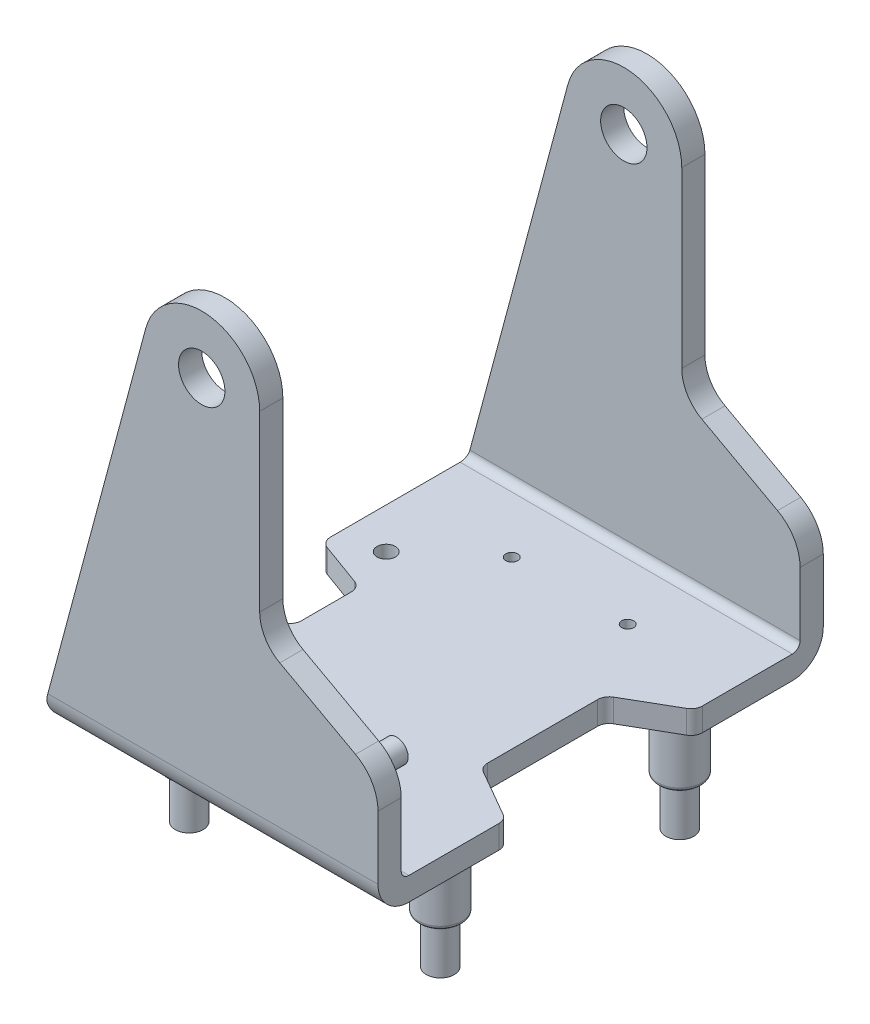
SolidWorks part; units mm, degrees
ref_plane "Front Plane" through (0, 0, 0) normal (0, 0, 1) x (1, 0, 0)
ref_plane "Top Plane" through (0, 0, 0) normal (0, 1, 0) x (1, 0, 0)
ref_plane "Right Plane" through (0, 0, 0) normal (1, 0, 0) x (0, 0, -1)
sketch "Sketch1" plane through (0, 0, 0) normal (0, 1, 0) x (1, 0, 0)
  line L0 (-32.5, 31) -> (-32.5, -31) construction
  line L1 (32.5, 31) -> (32.5, -31) construction
  line L2 (-32.5, 0) -> (32.5, 0) construction
  circle A0 centre (-32.5, 31) radius 3.625
  circle A1 centre (-32.5, -31) radius 3.625
  circle A2 centre (32.5, -31) radius 3.625
  circle A3 centre (32.5, 31) radius 3.625
  point P4 (32.5, 0)
  point P5 (-32.5, 0)
  point P13 (0, 0)
  dimension "D4" = 7.25
  dimension "D1" = 62
  dimension "D2" = 62
  dimension "D3" = 65
extrude "Boss-Extrude1" add sketch "Sketch1" against normal blind 29
sketch "Sketch2" plane through (0, 0, 0) normal (0, 1, 0) x (1, 0, 0)
  line L0 (-43, 34.625) -> (-32.5, 34.625) construction
  line L1 (-43, 57.625) -> (43, 57.625)
  line L2 (-43, 57.625) -> (-43, -57.625)
  line L3 (-43, -57.625) -> (43, -57.625)
  line L4 (43, 57.625) -> (43, -57.625)
  line L5 (-43, 57.625) -> (43, -57.625) construction
  line L6 (-43, -57.625) -> (43, 57.625) construction
  line L7 (-36.125, 57.625) -> (-36.125, 31) construction
  circle A0 centre (-32.5, 31) radius 3.625 construction
  point P0 (0, 0)
  dimension "D1" = 23
  dimension "D2" = 86
extrude "Boss-Extrude2" add sketch "Sketch2" along normal blind 6
sketch "Sketch4" plane through (0, 0, 57.625) normal (0, 0, 1) x (1, 0, 0)
  line L2 (43, 6) -> (-43, 6)
  line L3 (-43, 6) -> (-17.1181, 102.5926)
  line L4 (12.3708, 98.7103) -> (12.3708, 53.7103)
  line L6 (22.3708, 43.7103) -> (43, 43.7103)
  line L7 (43, 43.7103) -> (43, 6)
  arc A1 (-17.1181, 102.5926) -> (12.3708, 98.7103) centre (-2.6292, 98.7103) cw
  arc A2 (12.3708, 53.7103) -> (22.3708, 43.7103) centre (22.3708, 53.7103) ccw
  dimension "D3" = 15
  dimension "D5" = 10
  dimension "D1" = 75
  dimension "D2" = 100
  dimension "D4" = 45
  dimension "D7" = 15
extrude "Boss-Extrude3" add sketch "Sketch4" against normal blind 6
fillet "Fillet2" radius 10 1 edges at (43, 43.7103, 54.625)
mirror "Mirror1" about plane through (0, 0, 0) normal (0, 0, 1) of "Boss-Extrude3", "Fillet2"
sketch "Sketch5" plane through (0, 0, 0) normal (0, -1, 0) x (1, 0, 0)
  circle A0 centre (-32.5, -31) radius 3.625 construction
  circle A1 centre (32.5, -31) radius 3.625 construction
  circle A2 centre (32.5, 31) radius 3.625 construction
  circle A3 centre (-32.5, 31) radius 3.625 construction
  circle A4 centre (-32.5, -31) radius 3.625
  circle A5 centre (32.5, -31) radius 3.625
  circle A6 centre (32.5, 31) radius 3.625
  circle A7 centre (-32.5, 31) radius 3.625
  circle A8 centre (-32.5, 31) radius 5.625
  circle A9 centre (32.5, 31) radius 5.625
  circle A10 centre (32.5, -31) radius 5.625
  circle A11 centre (-32.5, -31) radius 5.625
  dimension "D1" = 2
extrude "Boss-Extrude4" add sketch "Sketch5" along normal blind 17
fillet "Fillet3" radius 2 4 edges at (32.5, 0, -25.375) (32.5, 0, 36.625) (-32.5, 0, 36.625) (-32.5, 0, -25.375)
fillet "Fillet4" radius 1 8 edges at (32.5, -17, -36.625) (32.5, -17, -34.625) (-32.5, -17, -36.625) (-32.5, -17, -34.625) (-32.5, -17, 25.375) (-32.5, -17, 27.375) (32.5, -17, 25.375) (32.5, -17, 27.375)
fillet "Fillet5" radius 8 2 edges at (0, 0, -57.625) (0, 0, 57.625)
fillet "Fillet6" radius 2 2 edges at (0, 6, -51.625) (0, 6, 51.625)
sketch "Sketch6" plane through (0, 6, 0) normal (0, 1, 0) x (1, 0, 0)
  line L0 (-43, 24.625) -> (-28, 15.9647)
  line L1 (-43, 49.625) -> (-43, -49.625) construction
  line L2 (-28, 15.9647) -> (-28, -15.9647)
  line L3 (-28, -15.9647) -> (-43, -24.625)
  line L4 (-43, -24.625) -> (-43, 24.625)
  dimension "D1" = 25
  dimension "D2" = 25
  dimension "D3" = 15
  dimension "D4" = 120
  dimension "D5" = 120
extrude "Cut-Extrude1" cut sketch "Sketch6" against normal through all both and the other way through all
mirror "Mirror2" about plane through (0, 0, 0) normal (1, 0, 0) of "Cut-Extrude1"
fillet "Fillet7" radius 3 8 edges at (-43, 3, 24.625) (-28, 3, 15.9647) (-43, 3, -24.625) (-28, 3, -15.9647) (43, 3, -24.625) (28, 3, -15.9647) (43, 3, 24.625) (28, 3, 15.9647)
sketch "Sketch7" plane through (0, 0, 57.625) normal (0, 0, 1) x (1, 0, 0)
  circle A0 centre (-2.6292, 98.7103) radius 6
  dimension "D1" = 12
extrude "Cut-Extrude2" cut sketch "Sketch7" against normal through all both
sketch "Sketch8" plane through (0, 0, 51.625) normal (0, 0, -1) x (-1, 0, 0)
  line L0 (-43, 8) -> (42.4641, 8) construction
  circle A2 centre (-31.8179, 24.4204) radius 3
  dimension "D1" = 6
  dimension "D2" = 11.1821
  dimension "D3" = 16.4204
sketch "Sketch9" plane through (0, 0, 51.625) normal (0, 0, -1) x (-1, 0, 0)
  line L0 (-43, 8) -> (42.4641, 8) construction
  circle A2 centre (21.2278, 17.4368) radius 3
  dimension "D1" = 9.4368
  dimension "D3" = 6
  dimension "D2" = 21.2363
extrude "Boss-Extrude6" add sketch "Sketch9" along normal blind 10
extrude "Boss-Extrude7" add sketch "Sketch8" along normal blind 10
fillet "Fillet8" radius 2 2 edges at (28.8179, 24.4204, 51.625) (-24.2278, 17.4368, 51.625)
sketch "Sketch12" plane through (0, 0, 0) normal (0, -1, 0) x (1, 0, 0)
  line L1 (-15, 35) -> (15, 35) construction
  line L2 (-15, 35) -> (-15, -35) construction
  line L3 (-15, -35) -> (15, -35) construction
  line L4 (15, 35) -> (15, -35) construction
  line L5 (-15, 35) -> (15, -35) construction
  line L6 (-15, -35) -> (15, 35) construction
  circle A0 centre (-15, 35) radius 1.55
  circle A1 centre (15, 35) radius 1.55
  circle A2 centre (15, -35) radius 1.55
  circle A3 centre (-15, -35) radius 1.55
  point P0 (0, 0)
  dimension "D3" = 3.1
  dimension "D1" = 30
  dimension "D2" = 70
extrude "Cut-Extrude3" cut sketch "Sketch12" against normal through all both and the other way through all
sketch "Sketch13" plane through (0, 6, 0) normal (0, 1, 0) x (1, 0, 0)
  line L0 (-41.5, -23.759) -> (-29.5, -16.8308) construction
  line L1 (-28, -14.2327) -> (-28, 14.2327) construction
  line L2 (-29.5, 16.8308) -> (-41.5, 23.759) construction
  line L3 (-41.5, -23.759) -> (-29.5, -16.8308)
  line L4 (-28, -14.2327) -> (-28, 14.2327)
  line L5 (-29.5, 16.8308) -> (-41.5, 23.759)
  line L6 (-43, -26.3571) -> (-43, 26.3571)
  arc A0 (-41.5, -23.759) -> (-43, -26.3571) centre (-40, -26.3571) ccw construction
  arc A1 (-29.5, -16.8308) -> (-28, -14.2327) centre (-31, -14.2327) ccw construction
  arc A2 (-28, 14.2327) -> (-29.5, 16.8308) centre (-31, 14.2327) ccw construction
  arc A3 (-43, 26.3571) -> (-41.5, 23.759) centre (-40, 26.3571) ccw construction
  arc A4 (-41.5, -23.759) -> (-43, -26.3571) centre (-40, -26.3571) ccw
  arc A5 (-29.5, -16.8308) -> (-28, -14.2327) centre (-31, -14.2327) ccw
  arc A6 (-28, 14.2327) -> (-29.5, 16.8308) centre (-31, 14.2327) ccw
  arc A7 (-43, 26.3571) -> (-41.5, 23.759) centre (-40, 26.3571) ccw
extrude "Boss-Extrude8" add sketch "Sketch13" against normal up to surface (6 mm away) up to face at (-15, 0, -33.45)
sketch "Sketch14" plane through (0, 6, 0) normal (0, 1, 0) x (1, 0, 0)
  line L0 (-43, 14) -> (-43, -14)
  line L1 (-43, 49.625) -> (-43, -49.625) construction
  line L2 (-43, -14) -> (-28, -8.5404)
  line L3 (-28, -8.5404) -> (-28, 8.5404)
  line L4 (-28, 8.5404) -> (-43, 14)
  point P7 (-43, 0)
  point P8 (-28, 0)
  dimension "D1" = 15
  dimension "D2" = 28
  dimension "D3" = 110
extrude "Cut-Extrude4" cut sketch "Sketch14" against normal blind 10
fillet "Fillet9" radius 3 4 edges at (-43, 3, 14) (-28, 3, 8.5404) (-28, 3, -8.5404) (-43, 3, -14)
sketch "Sketch15" plane through (0, 6, 0) normal (0, 1, 0) x (1, 0, 0)
  line L0 (-32.5, 20) -> (-32.5, -20) construction
  line L1 (-28, -6.4398) -> (-28, 6.4398) construction
  line L2 (-43, 49.625) -> (-43, 16.1006) construction
  circle A0 centre (-32.5, 20) radius 2.375
  circle A1 centre (-32.5, -20) radius 2.375
  point P4 (-28, 0)
  point P5 (-32.5, 0)
  dimension "D3" = 4.75
  dimension "D1" = 40
  dimension "D2" = 10.5
extrude "Cut-Extrude5" cut sketch "Sketch15" against normal blind 10
sketch "Sketch16" plane through (0, 0, 51.625) normal (0, 0, -1) x (-1, 0, 0)
  line L0 (-43, 33.7103) -> (-43, 8) construction
  line L1 (-17.5793, 44.933) -> (-37.1758, 34.2353)
  line L2 (-22.3708, 43.7103) -> (-47.7394, 43.7103)
  line L3 (-47.7394, 43.7103) -> (-47.7394, 24.4204)
  line L4 (-47.7394, 24.4204) -> (-43, 24.4204)
  circle A0 centre (-31.8179, 24.4204) radius 5 construction
  circle A1 centre (-31.8179, 24.4204) radius 5
  circle A2 centre (-31.8179, 24.4204) radius 11.1821
  circle A3 centre (-22.3708, 53.7103) radius 10
  line M5 (-43, 33.7103) -> (-43, 8)
  arc M10 (-12.3708, 53.7103) -> (-22.3708, 43.7103) centre (-22.3708, 53.7103) cw
  line M11 (-22.3708, 43.7103) -> (-33, 43.7103)
  arc M12 (-33, 43.7103) -> (-43, 33.7103) centre (-33, 33.7103) ccw
extrude "Cut-Extrude6" cut sketch "Sketch16" against normal through all both and the other way through all contours L3 L4 L2 M5 M12 | A2 L1 M10 M11 M12 M5 region at (34.6785, 38.6914, 51.625) region at (44.4946, 35.4743, 51.625)
